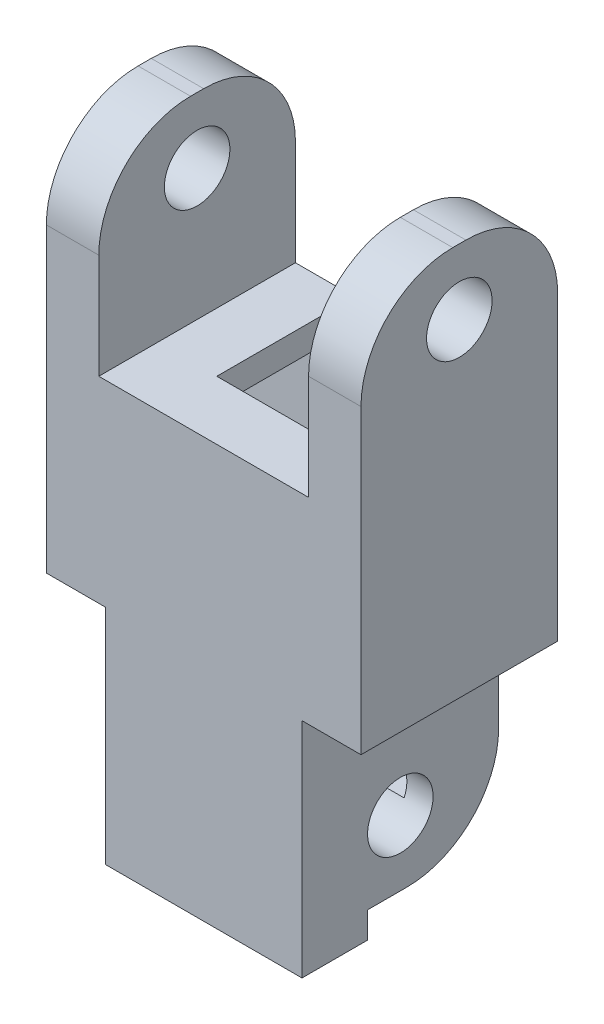
SolidWorks part; units mm, degrees
ref_plane "Front Plane" through (0, 0, 0) normal (0, 0, 1) x (1, 0, 0)
ref_plane "Top Plane" through (0, 0, 0) normal (0, 1, 0) x (1, 0, 0)
ref_plane "Right Plane" through (0, 0, 0) normal (1, 0, 0) x (0, 0, -1)
sketch "Sketch1" plane through (0, 0, 0) normal (0, 0, 1) x (1, 0, 0)
  line L0 (-12, 15) -> (-8, 15)
  line L1 (-8, 15) -> (-8, 0)
  line L2 (-8, 0) -> (8, 0)
  line L3 (8, 0) -> (8, 15)
  line L4 (8, 15) -> (12, 15)
  line L5 (12, 15) -> (12, -15)
  line L6 (12, -15) -> (7.5, -15)
  line L7 (7.5, -15) -> (7.5, -30)
  line L8 (7.5, -30) -> (-7.5, -30)
  line L10 (-7.5, -30) -> (-7.5, -15)
  line L11 (-7.5, -15) -> (-12, -15)
  line L12 (-12, -15) -> (-12, 15)
  line L14 (-10, -2) -> (10, -2)
  line L15 (-10, -2) -> (-10, -13)
  line L16 (-10, -13) -> (10, -13)
  line L17 (10, -2) -> (10, -13)
  line L18 (-10, -2) -> (10, -13) construction
  line L19 (-10, -13) -> (10, -2) construction
  line L20 (-5.5, -26) -> (5.5, -26)
  line L21 (-5.5, -26) -> (-5.5, -13)
  line L22 (-5.5, -13) -> (5.5, -13)
  line L23 (5.5, -26) -> (5.5, -13)
  point P19 (0, 0)
  point P20 (0, -7.5)
  dimension "D1" = 16
  dimension "D2" = 4
  dimension "D3" = 15
  dimension "D4" = 15
  dimension "D5" = 30
  dimension "D7" = 2
  dimension "D8" = 2
  dimension "D9" = 2
  dimension "D10" = 2
  dimension "D11" = 2
  dimension "D12" = 2
  dimension "D13" = 4
extrude "Boss-Extrude1" add sketch "Sketch1" along normal blind 15 contours L17 L14 L15 L16 | L12 L11 L10 L8 L7 L6 L5 L4 L3 L2 L1 L0 L14 L17 L16 L15 | L20 L23 L16 L21 region at (-10, 14.49, 0) region at (0, -7.5, 0) region at (0, -19.5, 0)
sketch "Sketch2" plane through (12, 0, 0) normal (1, 0, 0) x (0, 0, -1)
  line L0 (-15, 15) -> (0, 15) construction
  line L1 (0, 15) -> (0, -15) construction
  line L2 (-15, -30) -> (0, -30) construction
  circle A0 centre (-7.5, 10) radius 2.5
  circle A1 centre (-7.5, -25) radius 2.5
  point P4 (-7.5, 15)
  dimension "D1" = 5
  dimension "D2" = 5
  dimension "D3" = 7.5
  dimension "D4" = 5
extrude "Cut-Extrude1" cut sketch "Sketch2" against normal blind 36
sketch "Sketch3" plane through (0, 0, 0) normal (0, 1, 0) x (1, 0, 0)
  line L1 (-1.25, 0) -> (1.25, 0)
  line L2 (-1.25, 0) -> (-1.25, -1.5)
  line L4 (1.25, 0) -> (1.25, -1.5)
  line L5 (1.25, -1.5) -> (3.5, -1.5)
  line L6 (-3.5, -10.5) -> (3.5, -10.5)
  line L7 (-3.5, -10.5) -> (-3.5, -1.5)
  line L8 (-3.5, -1.5) -> (-1.25, -1.5)
  line L9 (3.5, -10.5) -> (3.5, -1.5)
  point P12 (0, 0)
  dimension "D1" = 1.5
  dimension "D2" = 9
  dimension "D3" = 7
  dimension "D4" = 2.5
extrude "Cut-Extrude2" cut sketch "Sketch3" against normal blind 36
extrude "Cut-Extrude3" cut sketch "Sketch1<3>" along normal blind 11 from offset 2 contours L17 L14 L15 L16 | L21 L20 L23 L22 region at (0, -7.5, 0)
sketch "Sketch1<3>" plane through (0, 0, 0) normal (0, 0, 1) x (1, 0, 0) same geometry as "Sketch1"
fillet "Fillet4" radius 7 6 edges at (10, 15, 15) (10, 15, 0) (-10, 15, 15) (-10, 15, 0) (4.375, -30, 0) (-4.375, -30, 0)
sketch "Sketch5" plane through (7.5, 0, 0) normal (1, 0, 0) x (0, 0, -1)
  line L1 (-15, -30) -> (-10, -30)
  line L2 (-15, -30) -> (-15, -32)
  line L3 (-15, -32) -> (-10, -32)
  line L4 (-10, -30) -> (-10, -32)
  dimension "D1" = 2
  dimension "D2" = 5
extrude "Boss-Extrude2" add sketch "Sketch5" against normal up to surface (15 mm away) up to face at (-7.5, -25, 10)
